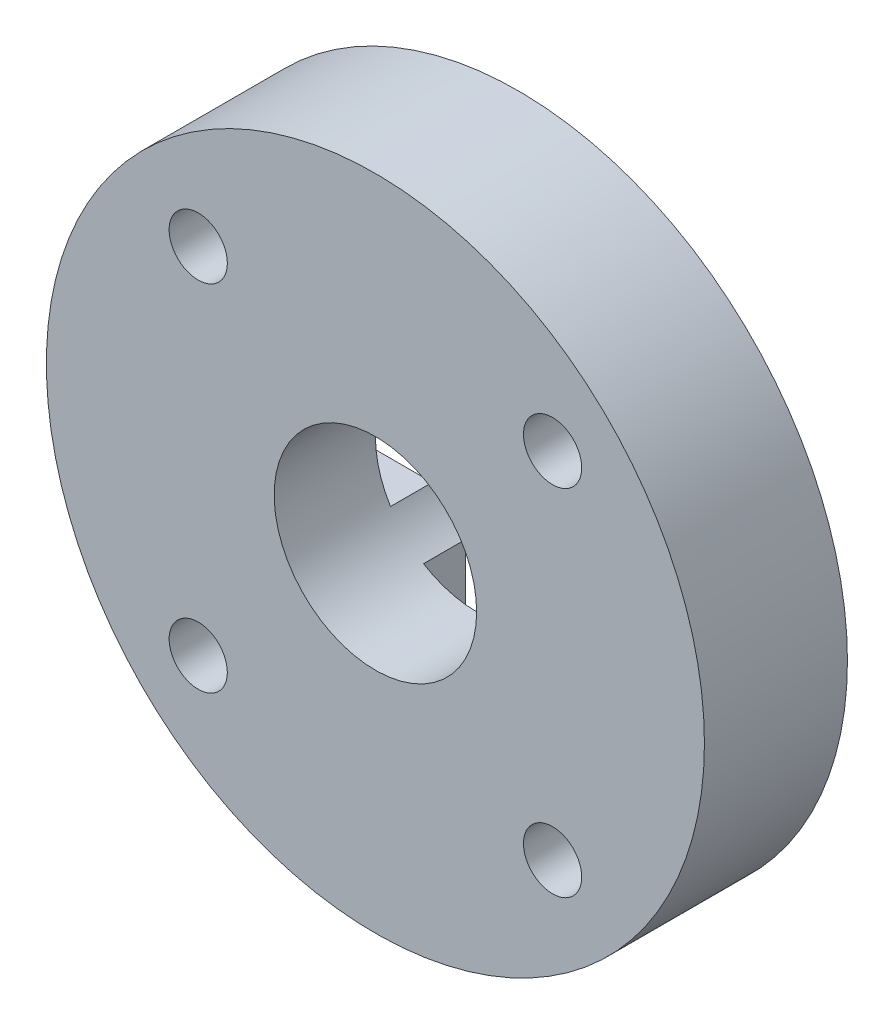
SolidWorks part; units mm, degrees
ref_plane "Front Plane" through (0, 0, 0) normal (0, 0, 1) x (1, 0, 0)
ref_plane "Top Plane" through (0, 0, 0) normal (0, 1, 0) x (1, 0, 0)
ref_plane "Right Plane" through (0, 0, 0) normal (1, 0, 0) x (0, 0, -1)
sketch "Trial_load_plate_profile" plane through (0, 0, 0) normal (0, 0, 1) x (1, 0, 0)
  circle A0 centre (0, 0) radius 13
  circle A1 centre (0, 0) radius 4
  dimension "D1" = 26
  dimension "D2" = 8
extrude "Trial_load_plate" add sketch "Trial_load_plate_profile" along normal blind 4
sketch "Captured_horn_key_boss_profile" plane through (0, 0, 0) normal (0, 0, 1) x (1, 0, 0)
  circle A0 centre (0, 0) radius 13
  dimension "D1" = 26
extrude "Captured_horn_key_boss" add sketch "Captured_horn_key_boss_profile" along normal blind 1.65 from offset 1.65 offset against normal yes
sketch "Stock_horn_pocket_Hub" plane through (0, 0, 0) normal (0, 0, 1) x (1, 0, 0)
  circle A0 centre (0, 0) radius 3.55
  dimension "D1" = 7.1
extrude "Key_pocket_Hub" cut sketch "Stock_horn_pocket_Hub" along normal blind 1.65 from offset 1.65 offset against normal yes
sketch "Stock_horn_pocket_Horizontal" plane through (0, 0, 0) normal (0, 0, 1) x (1, 0, 0)
  line L1 (-8.15, -2.1) -> (8.15, -2.1)
  line L2 (-8.15, -2.1) -> (-8.15, 2.1)
  line L3 (-8.15, 2.1) -> (8.15, 2.1)
  line L4 (8.15, -2.1) -> (8.15, 2.1)
  dimension "D1" = 16.3
  dimension "D2" = 4.2
  dimension "D3" = 8.15
  dimension "D4" = 2.1
extrude "Key_pocket_Horizontal" cut sketch "Stock_horn_pocket_Horizontal" along normal blind 1.65 from offset 1.65 offset against normal yes
sketch "Stock_horn_pocket_Vertical" plane through (0, 0, 0) normal (0, 0, 1) x (1, 0, 0)
  line L1 (-2.1, -8.15) -> (2.1, -8.15)
  line L2 (-2.1, -8.15) -> (-2.1, 8.15)
  line L3 (-2.1, 8.15) -> (2.1, 8.15)
  line L4 (2.1, -8.15) -> (2.1, 8.15)
  dimension "D1" = 4.2
  dimension "D2" = 16.3
  dimension "D3" = 2.1
  dimension "D4" = 8.15
extrude "Key_pocket_Vertical" cut sketch "Stock_horn_pocket_Vertical" along normal blind 1.65 from offset 1.65 offset against normal yes
sketch "Stock_horn_pocket_Rounded_tips" plane through (0, 0, 0) normal (0, 0, 1) x (1, 0, 0)
  circle A0 centre (8.15, 0) radius 2.1
  circle A1 centre (-8.15, 0) radius 2.1
  circle A2 centre (0, 8.15) radius 2.1
  circle A3 centre (0, -8.15) radius 2.1
  dimension "D1" = 4.2
  dimension "D2" = 4.2
  dimension "D3" = 4.2
  dimension "D4" = 4.2
  dimension "D5" = 8.15
  dimension "D6" = 8.15
  dimension "D7" = 8.15
  dimension "D8" = 8.15
extrude "Key_pocket_Rounded_tips" cut sketch "Stock_horn_pocket_Rounded_tips" along normal blind 1.65 from offset 1.65 offset against normal yes
sketch "Unmodified_horn_capture_M2_profile" plane through (0, 0, 0) normal (0, 0, 1) x (1, 0, 0)
  circle A0 centre (7, 7) radius 1.15
  circle A1 centre (-7, 7) radius 1.15
  circle A2 centre (-7, -7) radius 1.15
  circle A3 centre (7, -7) radius 1.15
  dimension "D1" = 2.3
  dimension "D2" = 2.3
  dimension "D3" = 2.3
  dimension "D4" = 2.3
  dimension "D5" = 7
  dimension "D6" = 7
  dimension "D7" = 7
  dimension "D8" = 7
extrude "Unmodified_horn_capture_M2" cut sketch "Unmodified_horn_capture_M2_profile" along normal through all from offset 50 offset against normal yes
sketch "Horn_center_hub_clearance" plane through (0, 0, 0) normal (0, 0, 1) x (1, 0, 0)
  circle A0 centre (0, 0) radius 4
  dimension "D1" = 8
extrude "Hub_clearance_in_key_boss_only" cut sketch "Horn_center_hub_clearance" along normal blind 1.65 from offset 1.65 offset against normal yes
